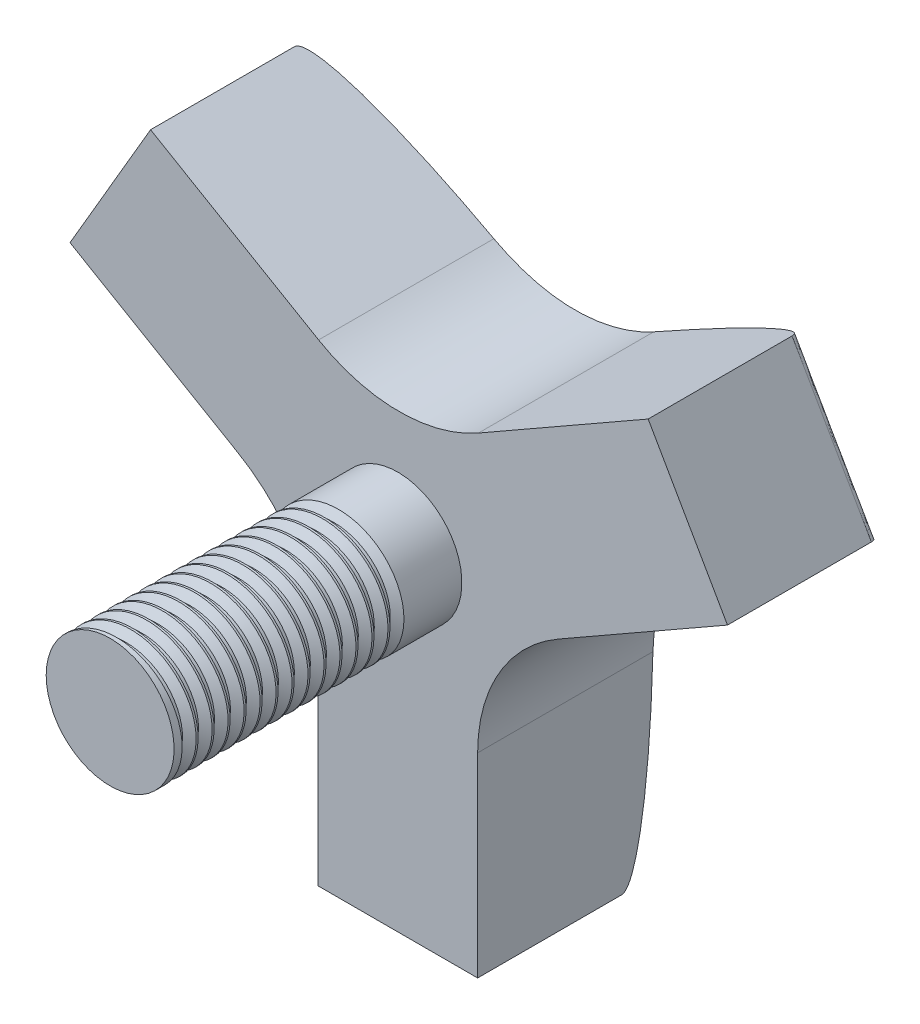
SolidWorks part; units mm, degrees
ref_plane "Alzado" through (0, 0, 0) normal (0, 0, 1) x (1, 0, 0)
ref_plane "Planta" through (0, 0, 0) normal (0, 1, 0) x (1, 0, 0)
ref_plane "Vista lateral" through (0, 0, 0) normal (1, 0, 0) x (0, 0, -1)
sketch "Croquis2" plane through (0, 0, 0) normal (0, 0, 1) x (1, 0, 0)
  line L0 (5.0382, 8.6381) -> (15.6536, 14.7045)
  line L1 (0.0255, 5.7734) -> (-5.0127, -2.8646)
  line L2 (-5.0127, -2.8646) -> (4.9872, -2.9088)
  line L3 (4.9872, -2.9088) -> (0.0255, 5.7734)
  line L4 (15.6536, 14.7045) -> (20.6153, 6.0222)
  line L5 (20.6153, 6.0222) -> (10.0255, -0.0296)
  line L6 (4.9872, -8.7118) -> (4.9872, -20.9088)
  line L7 (4.9872, -20.9088) -> (-5.0127, -20.9088)
  line L8 (-5.0127, -20.9088) -> (-5.0127, -8.6087)
  line L9 (-9.9745, 0.0294) -> (-20.5103, 6.1745)
  line L10 (-20.5103, 6.1745) -> (-15.4721, 14.8126)
  line L11 (-15.4721, 14.8126) -> (-4.9617, 8.6823)
  circle A0 centre (0, 0) radius 2.8868 construction
  arc A1 (-9.9745, 0.0294) -> (-5.0127, -8.6087) centre (-15.0127, -8.6087) cw
  arc A2 (4.9872, -8.7118) -> (10.0255, -0.0296) centre (14.9872, -8.7118) cw
  arc A3 (5.0382, 8.6381) -> (-4.9617, 8.6823) centre (0.0766, 17.3203) cw
  dimension "D5" = 10
  dimension "D1" = 90
  dimension "D2" = 90
  dimension "D3" = 10
  dimension "D4" = 18
extrude "Saliente-Extruir1" add sketch "Croquis2" along normal blind 11 contours A3 L0 L4 L5 A2 L6 L7 L8 A1 L9 L10 L11
sketch "Croquis6" plane through (0, 0, 11) normal (0, 0, 1) x (1, 0, 0)
  circle A0 centre (0, 0) radius 4
  dimension "D1" = 8
extrude "Saliente-Extruir2" add sketch "Croquis6" along normal blind 18
thread "Rosca1" pitch 1 method cut profile "Perfil de rosca1" start angle 0, offset 0, length 14, pitch 1, diameter 8
ref_plane "Plano1" through (-4, 0, 29) normal (0, -1, 0) x (-1, 0, 0)
sketch "Perfil de rosca1" plane through (-4, 0, 29) normal (0, -1, 0) x (-1, 0, 0)
  line L0 (0, 0) -> (0, 1) construction
  line L11 (0, 0) -> (0, 0.875)
  line L12 (0, 0.875) -> (-0.5413, 0.5625)
  line L13 (-0.5413, 0.5625) -> (-0.5413, 0.3125)
  line L15 (-0.5413, 0.3125) -> (0, 0)
  line L17 (-0.5413, 0.4375) -> (0, 0.4375) construction
  point P2 (0, 0)
  dimension "Pitch" = 1
  dimension "Profile_Angle" = 60
  dimension "Profile_Land" = 0.25
  dimension "Profile_Height" = 0.5413
ref_axis "Eje1" through (0, 0, -31.663) along (0, 0, 1)
fillet "Redondeo1" radius 2 3 edges at (-17.9912, 10.4935, 0) (18.1344, 10.3633, 0) (-0.0128, -20.9088, 0) second distance 15 first distance on face at (-17.9912, 10.4935, 5.5) first distance on face at (18.1344, 10.3633, 5.5) first distance on face at (-0.0128, -20.9088, 5.5)
split "Partir1" bodies to split 104 resulting bodies 105 106 split by face at (-4, 0, 11)
